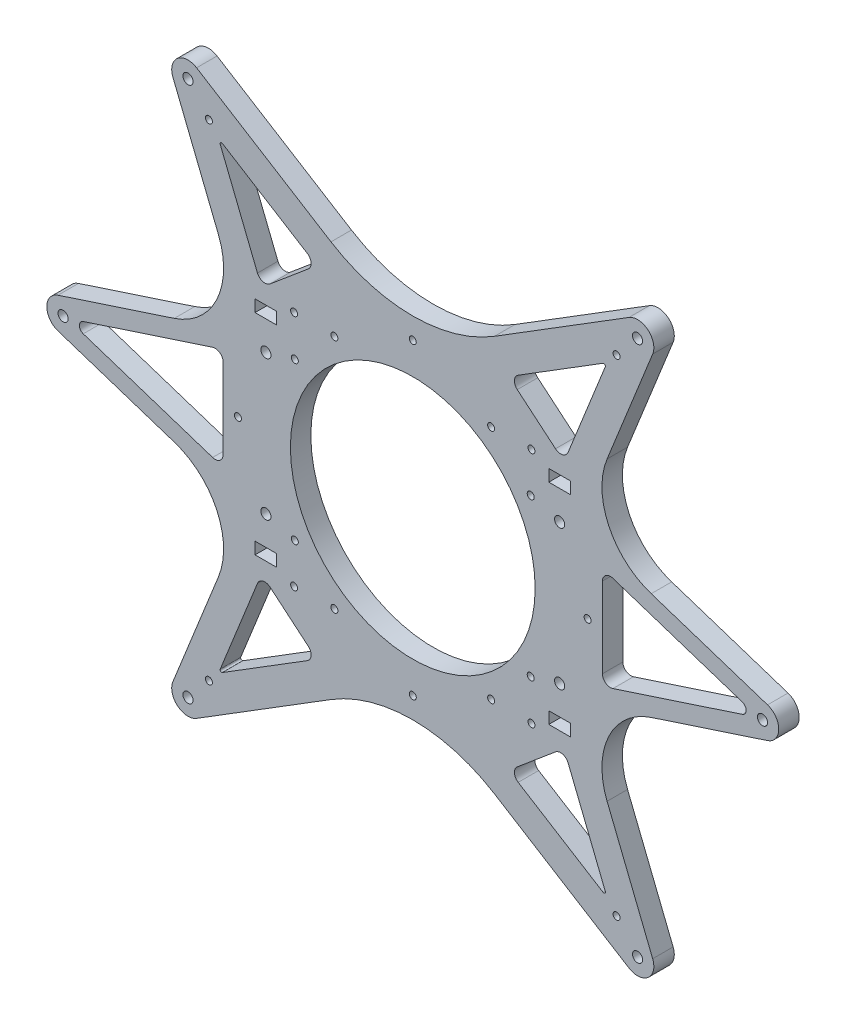
SolidWorks part; units mm, degrees
material "Acrylic (Medium-high impact)"
ref_plane "Front Plane" through (0, 0, 0) normal (0, 0, 1) x (1, 0, 0)
ref_plane "Top Plane" through (0, 0, 0) normal (0, 1, 0) x (1, 0, 0)
ref_plane "Right Plane" through (0, 0, 0) normal (1, 0, 0) x (0, 0, -1)
sketch "Sketch1" plane through (0, 0, 0) normal (0, 0, 1) x (1, 0, 0)
  line L0 (-447622.4345, 422.8828) -> (448935.6268, 422.8828) construction
  line L1 (587.9953, 497.7534) -> (601.0264, 465.2697)
  line L2 (698.5962, 452.8828) -> (698.5962, 392.8828) construction
  line L3 (653.3971, 419.0702) -> (-31485.9834, -37883.1519) construction
  line L4 (701.6962, 394.5828) -> (695.4962, 391.1828) construction
  line L5 (701.6962, 391.1828) -> (695.4962, 394.5828) construction
  line L6 (626.4541, 473.2977) -> (602.1777, 488.3841)
  line L7 (594.7755, 503.4426) -> (633.2109, 479.5572)
  line L8 (601.5396, 487.8487) -> (612.1813, 461.3214)
  line L9 (598.3082, 492.3477) -> (598.7333, 491.841) construction
  line L10 (701.6962, 391.1828) -> (695.4962, 391.1828)
  line L11 (695.4962, 394.5828) -> (695.4962, 391.1828)
  line L12 (701.6962, 394.5828) -> (695.4962, 394.5828)
  line L13 (594.7755, 503.4426) -> (587.9953, 497.7534) construction
  line L14 (626.7171, 469.6022) -> (615.775, 460.4206)
  line L15 (686.4752, 469.6022) -> (697.4174, 460.4206)
  line L16 (701.6962, 394.5828) -> (701.6962, 391.1828)
  line L17 (-343.4038, 422.8828) -> (49656.5962, 422.8828) construction
  line L18 (648.8948, 432.061) -> (-31490.4849, 38734.2822) construction
  line L19 (-347.3366, 472.8828) -> (49652.6634, 472.8828) construction
  line L20 (-347.2527, 372.8828) -> (49652.7473, 372.8828) construction
  line L21 (562.3601, 421.3552) -> (599.3601, 409.2322)
  line L22 (602.3601, 434.3594) -> (602.3601, 411.4062)
  line L23 (555.1462, 427.3082) -> (555.1462, 418.4573) construction
  line L24 (562.3601, 424.4103) -> (599.3601, 436.5334)
  line L25 (599.3601, 409.2322) -> (599.3601, 436.5334) construction
  line L26 (555.1462, 427.3082) -> (588.4064, 438.2059)
  line L27 (562.3601, 421.3552) -> (562.3601, 424.4103) construction
  line L28 (555.1462, 418.4573) -> (588.4064, 407.5596)
  line L29 (686.7382, 473.2977) -> (711.0147, 488.3841)
  line L30 (594.7755, 342.3229) -> (633.2109, 366.2084)
  line L31 (711.6527, 487.8487) -> (701.0111, 461.3214)
  line L32 (611.4962, 451.1828) -> (617.6962, 454.5828) construction
  line L33 (611.4962, 454.5828) -> (617.6962, 451.1828) construction
  line L34 (601.5396, 357.9169) -> (612.1813, 384.4442)
  line L35 (587.9953, 348.0122) -> (594.7755, 342.3229) construction
  line L36 (626.4541, 372.4678) -> (602.1777, 357.3814)
  line L37 (626.7171, 376.1634) -> (615.775, 385.3449)
  line L38 (587.9953, 348.0122) -> (601.0264, 380.4959)
  line L39 (611.4962, 391.1828) -> (617.6962, 394.5828) construction
  line L40 (701.6962, 454.5828) -> (695.4962, 451.1828) construction
  line L41 (611.4962, 394.5828) -> (617.6962, 391.1828) construction
  line L42 (614.5962, 452.8828) -> (614.5962, 392.8828) construction
  line L43 (701.6962, 451.1828) -> (695.4962, 454.5828) construction
  line L44 (686.4752, 376.1634) -> (697.4174, 385.3449)
  line L45 (725.1971, 348.0122) -> (718.4169, 342.3229) construction
  line L46 (711.6527, 357.9169) -> (701.0111, 384.4442)
  line L47 (750.8323, 421.3552) -> (750.8323, 424.4103) construction
  line L48 (713.8323, 409.2322) -> (713.8323, 436.5334) construction
  line L49 (758.0462, 427.3082) -> (758.0462, 418.4573) construction
  line L50 (686.7382, 372.4678) -> (711.0147, 357.3814)
  line L51 (718.4169, 503.4426) -> (725.1971, 497.7534) construction
  line L53 (611.4962, 454.5828) -> (617.6962, 454.5828)
  line L54 (617.6962, 451.1828) -> (617.6962, 454.5828)
  line L55 (611.4962, 451.1828) -> (617.6962, 451.1828)
  line L56 (701.6962, 451.1828) -> (701.6962, 454.5828)
  line L57 (701.6962, 451.1828) -> (695.4962, 451.1828)
  line L58 (695.4962, 451.1828) -> (695.4962, 454.5828)
  line L59 (701.6962, 454.5828) -> (695.4962, 454.5828)
  line L60 (725.1971, 348.0122) -> (712.166, 380.4959)
  line L63 (718.4169, 342.3229) -> (679.9814, 366.2084)
  line L65 (758.0462, 418.4573) -> (724.786, 407.5596)
  line L66 (758.0462, 427.3082) -> (724.786, 438.2059)
  line L67 (750.8323, 424.4103) -> (713.8323, 436.5334)
  line L68 (710.8323, 434.3594) -> (710.8323, 411.4062)
  line L69 (750.8323, 421.3552) -> (713.8323, 409.2322)
  line L70 (611.4962, 451.1828) -> (611.4962, 454.5828)
  line L72 (611.4962, 394.5828) -> (611.4962, 391.1828)
  line L73 (611.4962, 394.5828) -> (617.6962, 394.5828)
  line L74 (617.6962, 394.5828) -> (617.6962, 391.1828)
  line L76 (718.4169, 503.4426) -> (679.9814, 479.5572)
  line L78 (725.1971, 497.7534) -> (712.166, 465.2697)
  line L79 (611.4962, 391.1828) -> (617.6962, 391.1828)
  line L80 (706.5962, 432.8828) -> (698.5962, 432.8828) construction
  line L82 (656.5962, 378.8828) -> (646.5962, 378.8828) construction
  line L83 (656.5962, 466.8828) -> (646.5962, 466.8828) construction
  line L84 (-50.5106, -284.224) -> (35304.8285, 35071.1151) construction
  line L85 (-50.5106, -284.224) -> (35304.8285, 35071.1151) construction
  line L86 (1363.703, -284.224) -> (-33991.6361, 35071.1151) construction
  line L91 (598.3082, 492.3477) -> (595.2884, 495.9465) construction
  line L92 (592.3174, 499.4872) -> (598.3082, 492.3477) construction
  line L111 (656.5962, -513.6368) -> (656.5962, 49486.3632) construction
  arc A0 (601.5396, 487.8487) -> (602.1777, 488.3841) centre (601.9464, 488.0119) cw
  arc A1 (587.9953, 497.7534) -> (594.7755, 503.4426) centre (592.3174, 499.4872) cw
  circle A2 centre (592.3174, 499.4872) radius 1.45
  arc A4 (612.1813, 461.3214) -> (615.775, 460.4206) centre (614.3045, 462.1731) ccw
  arc A5 (626.4541, 473.2977) -> (626.7171, 469.6022) centre (625.2466, 471.3546) cw
  circle A6 centre (592.3174, 499.4872) radius 4.6569 construction
  circle A7 centre (622.6551, 456.8239) radius 1
  circle A8 centre (614.5962, 442.8828) radius 1.45
  circle A9 centre (690.5373, 456.8239) radius 1
  circle A10 centre (679.0129, 456.6132) radius 1
  arc A11 (555.1462, 418.4573) -> (555.1462, 427.3082) centre (556.5962, 422.8828) cw
  circle A12 centre (556.5962, 422.8828) radius 1.45
  circle A13 centre (690.3266, 445.2995) radius 1
  circle A14 centre (556.5962, 422.8828) radius 4.6569 construction
  arc A15 (562.3601, 424.4103) -> (562.3601, 421.3552) centre (562.8606, 422.8828) ccw
  circle A16 centre (656.5962, 422.8828) radius 35
  arc A18 (711.6527, 487.8487) -> (711.0147, 488.3841) centre (711.246, 488.0119) ccw
  arc A19 (602.3601, 434.3594) -> (599.3601, 436.5334) centre (600.0724, 434.3594) ccw
  arc A20 (686.7382, 473.2977) -> (686.4752, 469.6022) centre (687.9457, 471.3546) ccw
  arc A21 (599.3601, 409.2322) -> (602.3601, 411.4062) centre (600.0724, 411.4062) ccw
  circle A22 centre (656.5962, 466.8828) radius 1
  arc A23 (701.0111, 461.3214) -> (697.4174, 460.4206) centre (698.8879, 462.1731) cw
  circle A24 centre (592.3174, 346.2783) radius 4.6569 construction
  circle A25 centre (714.8842, 492.3477) radius 1
  arc A27 (594.7755, 342.3229) -> (587.9953, 348.0122) centre (592.3174, 346.2783) cw
  circle A28 centre (634.1795, 389.1524) radius 1
  circle A29 centre (622.6551, 388.9417) radius 1
  circle A31 centre (592.3174, 346.2783) radius 1.45
  circle A32 centre (622.8658, 400.4661) radius 1
  arc A33 (588.4064, 407.5596) -> (601.0264, 380.4959) centre (582.0351, 388.1144) cw
  circle A34 centre (656.5962, 378.8828) radius 1
  arc A35 (588.4064, 438.2059) -> (601.0264, 465.2697) centre (582.0351, 457.6512) ccw
  circle A37 centre (698.5962, 442.8828) radius 1.45
  circle A38 centre (698.5962, 402.8828) radius 1.45
  arc A39 (633.2109, 366.2084) -> (656.5962, 372.8828) centre (656.5962, 328.5778) cw
  arc A40 (633.2109, 479.5572) -> (656.5962, 472.8828) centre (656.5962, 517.1878) ccw
  circle A41 centre (720.8749, 346.2783) radius 4.6569 construction
  circle A42 centre (756.5962, 422.8828) radius 4.6569 construction
  circle A43 centre (598.3082, 353.4179) radius 1
  circle A44 centre (622.8658, 445.2995) radius 1
  circle A45 centre (634.1795, 456.6132) radius 1
  circle A46 centre (720.8749, 499.4872) radius 4.6569 construction
  circle A47 centre (598.3082, 492.3477) radius 1
  arc A48 (601.5396, 357.9169) -> (602.1777, 357.3814) centre (601.9464, 357.7537) ccw
  arc A49 (626.4541, 372.4678) -> (626.7171, 376.1634) centre (625.2466, 374.4109) ccw
  circle A50 centre (706.5962, 422.8828) radius 1
  arc A51 (679.9814, 479.5572) -> (656.5962, 472.8828) centre (656.5962, 517.1878) cw
  arc A52 (679.9814, 366.2084) -> (656.5962, 372.8828) centre (656.5962, 328.5778) ccw
  arc A53 (612.1813, 384.4442) -> (615.775, 385.3449) centre (614.3045, 383.5924) cw
  circle A54 centre (679.0129, 389.1524) radius 1
  arc A55 (724.786, 438.2059) -> (712.166, 465.2697) centre (731.1572, 457.6512) cw
  arc A56 (724.786, 407.5596) -> (712.166, 380.4959) centre (731.1572, 388.1144) ccw
  circle A57 centre (690.5373, 388.9417) radius 1
  circle A58 centre (720.8749, 346.2783) radius 1.45
  circle A59 centre (690.3266, 400.4661) radius 1
  circle A60 centre (714.8842, 353.4179) radius 1
  arc A61 (718.4169, 342.3229) -> (725.1971, 348.0122) centre (720.8749, 346.2783) ccw
  arc A62 (711.6527, 357.9169) -> (711.0147, 357.3814) centre (711.246, 357.7537) cw
  arc A63 (713.8323, 409.2322) -> (710.8323, 411.4062) centre (713.12, 411.4062) cw
  arc A64 (710.8323, 434.3594) -> (713.8323, 436.5334) centre (713.12, 434.3594) cw
  arc A65 (701.0111, 384.4442) -> (697.4174, 385.3449) centre (698.8879, 383.5924) ccw
  arc A66 (750.8323, 424.4103) -> (750.8323, 421.3552) centre (750.3318, 422.8828) cw
  arc A67 (686.7382, 372.4678) -> (686.4752, 376.1634) centre (687.9457, 374.4109) cw
  circle A68 centre (756.5962, 422.8828) radius 1.45
  arc A69 (758.0462, 418.4573) -> (758.0462, 427.3082) centre (756.5962, 422.8828) ccw
  circle A71 centre (606.5962, 422.8828) radius 1
  circle A76 centre (720.8749, 499.4872) radius 1.45
  arc A77 (725.1971, 497.7534) -> (718.4169, 503.4426) centre (720.8749, 499.4872) ccw
  circle A79 centre (614.5962, 402.8828) radius 1.45
  point P2 (621.2461, 465.0114)
  point P4 (604.6798, 472.924)
  point P5 (610.6788, 407.5004)
  point P6 (604.4937, 430.5743)
  point P7 (590.1096, 382.987)
  point P9 (656.5962, 422.8828)
  point P10 (592.2236, 451.9603)
  point P12 (560.2236, 451.9603)
  point P13 (615.5787, 412.0526)
  point P15 (596.4648, 452.5325)
  point P16 (593.7956, 519.1439)
  point P18 (562.0153, 451.7438)
  point P19 (589.324, 503.0546)
  point P21 (557.1601, 445.912)
  point P22 (691.7574, 496.0365)
  point P23 (586.2073, 519.1355)
  point P25 (698.5962, 452.8828)
  point P27 (593.4054, 384.161)
  point P31 (706.9167, 384.1702)
  point P32 (709.3005, 386.1481)
  point P33 (712.3266, 520.5499)
  point P34 (710.2125, 451.5766)
  point P37 (593.7956, 519.1439)
  point P38 (704.5328, 382.1922)
  point P40 (675.1867, 401.4708)
  point P41 (685.2778, 409.8289)
  point P43 (705.5495, 376.706)
  point P44 (637.2651, 404.097)
  point P46 (743.1543, 445.9191)
  point P47 (656.5962, 422.8828)
  point P48 (685.1467, 493.2598)
  point P49 (742.2125, 451.5766)
  point P53 (695.1768, 484.8286)
  point P55 (708.8884, 517.1528)
  point P56 (706.5155, 519.1439)
  point P57 (714.1038, 519.1355)
  point P64 (708.6406, 384.393)
  point P66 (665.171, 499.4399)
  point P67 (704.1427, 521.135)
  point P80 (602.3601, 422.8828)
  point P86 (499.5503, 435.3778)
  point P114 (563.3616, 328.8714)
  point P127 (698.5962, 422.8828)
  point P132 (656.5962, 457.8828)
  point P136 (656.5962, 465.8828)
  point P143 (704.687, 438.4721)
  point P145 (738.2906, 448.6533)
  point P146 (704.7346, 451.575)
  point P147 (738.2991, 451.7509)
  point P148 (738.3077, 454.8484)
  point P244 (749.8308, 328.8714)
  point P246 (710.8323, 422.8828)
  point P247 (698.5962, 422.8828)
  point P248 (723.8684, 503.0546)
  dimension "D2" = 2.9
  dimension "D6" = 8
  dimension "D9" = 48
  dimension "D7" = 8
  dimension "D11" = 100
  dimension "D12" = 9.32
  dimension "D5" = 10
  dimension "D19" = 50
  dimension "D20" = 100
  dimension "D25" = 6.2644
  dimension "D15" = 5.66
  dimension "D18" = 42
  dimension "D23" = 10
  dimension "D28" = 10
  dimension "D39" = 3.4
  dimension "D37" = 2
  dimension "D38" = 70
  dimension "D40" = 8
  dimension "D8" = 50
  dimension "D10" = 30
  dimension "D14" = 50
  dimension "D16" = 37
  dimension "D21" = 44
  dimension "D22" = 35
  dimension "D24" = 5
  dimension "D26" = 3
  dimension "D27" = 8
  dimension "D34" = 100
  dimension "D41" = 6.2
  dimension "D43" = 40.5
  dimension "D44" = 40.5
extrude "Boss-Extrude1" add sketch "Sketch1" along normal blind 5.85
